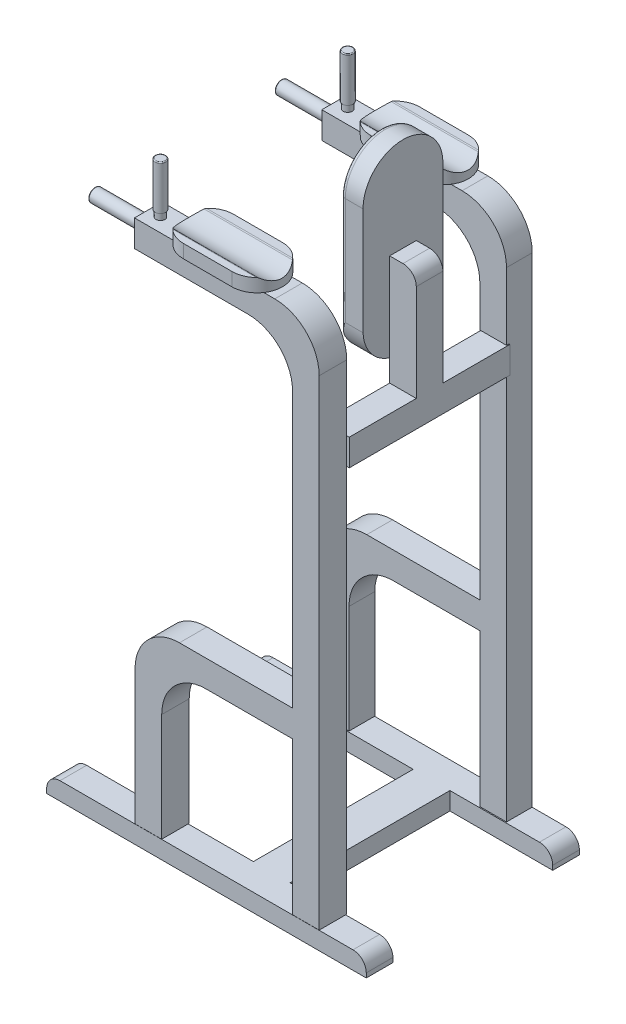
SolidWorks part; units mm, degrees
other "Camera1"
other "Camera2"
ref_plane "Front Plane" through (0, 0, 0) normal (0, 0, 1) x (1, 0, 0)
ref_plane "Top Plane" through (0, 0, 0) normal (0, 1, 0) x (1, 0, 0)
ref_plane "Right Plane" through (0, 0, 0) normal (1, 0, 0) x (0, 0, -1)
sketch "Sketch1" plane through (0, 0, 0) normal (0, 1, 0) x (1, 0, 0)
  line L0 (0, 0) -> (0, 76.2)
  line L1 (0, 76.2) -> (914.4, 76.2)
  line L2 (914.4, 76.2) -> (914.4, 0)
  line L3 (914.4, 0) -> (620.3894, 0)
  line L4 (620.3894, 0) -> (620.3894, -457.2)
  line L5 (620.3894, -457.2) -> (914.4, -457.2)
  line L6 (914.4, -457.2) -> (914.4, -533.4)
  line L7 (914.4, -533.4) -> (0, -533.4)
  line L8 (0, -533.4) -> (0, -457.2)
  line L9 (0, -457.2) -> (515.1929, -457.2)
  line L10 (515.1929, -457.2) -> (515.1929, 0)
  line L11 (515.1929, 0) -> (0, 0)
  dimension "D1" = 914.4
  dimension "D2" = 76.2
  dimension "D3" = 76.2
  dimension "D4" = 457.2
extrude "Boss-Extrude1" add sketch "Sketch1" along normal blind 50.8
fillet "Fillet1" radius 38.1 4 edges at (914.4, 50.8, 495.3) (914.4, 50.8, -38.1) (0, 50.8, -38.1) (0, 50.8, 495.3)
ref_plane "Plane1" through (0, 0, 535.94) normal (0, 0, 1) x (1, 0, 0)
sketch "Sketch2" plane through (0, 0, 535.94) normal (0, 0, 1) x (1, 0, 0)
  line L0 (331.6555, 53.7812) -> (331.6555, 362.6365)
  line L1 (458.6555, 489.6365) -> (706.0055, 489.6365)
  line L2 (706.0055, 489.6365) -> (706.0055, 53.7812)
  line L3 (706.0055, 53.7812) -> (782.2055, 53.7812)
  line L4 (782.2055, 53.7812) -> (782.2055, 1427.3864)
  line L5 (655.2055, 1554.3864) -> (253.8099, 1554.3864)
  line L6 (253.8099, 1554.3864) -> (253.8099, 1478.1864)
  line L7 (253.8099, 1478.1864) -> (579.0055, 1478.1864)
  line L8 (706.0055, 1351.1864) -> (706.0055, 565.8365)
  line L9 (706.0055, 565.8365) -> (382.4555, 565.8365)
  line L10 (255.4555, 438.8365) -> (255.4555, 53.7812)
  line L11 (255.4555, 53.7812) -> (331.6555, 53.7812)
  arc A0 (331.6555, 362.6365) -> (458.6555, 489.6365) centre (458.6555, 362.6365) cw
  arc A1 (382.4555, 565.8365) -> (255.4555, 438.8365) centre (382.4555, 438.8365) ccw
  arc A2 (782.2055, 1427.3864) -> (655.2055, 1554.3864) centre (655.2055, 1427.3864) ccw
  arc A3 (579.0055, 1478.1864) -> (706.0055, 1351.1864) centre (579.0055, 1351.1864) cw
  point P18 (782.2055, 1554.3864)
  dimension "D6" = 127
  dimension "D1" = 528.3956
  dimension "D2" = 76.2
  dimension "D3" = 76.2
  dimension "D4" = 76.2
  dimension "D5" = 76.2
extrude "Boss-Extrude2" add sketch "Sketch2" against normal blind 609.6 separate body
sketch "Sketch3" plane through (255.4555, 0, 0) normal (-1, 0, 0) x (0, 0, 1)
  line L0 (0, 50.8) -> (0, 1554.3864)
  line L1 (-73.66, 1554.3864) -> (535.94, 1554.3864) construction
  line L2 (0, 50.8) -> (457.2, 50.8)
  line L3 (457.2, 50.8) -> (457.2, 1554.3864)
  line L4 (457.2, 1554.3864) -> (0, 1554.3864)
extrude "Cut-Extrude1" cut sketch "Sketch3" against normal through all both and the other way through all
ref_plane "Plane2" through (784.7455, 0, 0) normal (1, 0, 0) x (0, 0, -1)
sketch "Sketch6" plane through (784.7455, 0, 0) normal (1, 0, 0) x (0, 0, -1)
  line L0 (7.3557, 1234.749) -> (-184.4143, 1234.749)
  line L1 (-452.3843, 1158.549) -> (7.3557, 1158.549)
  line L2 (7.3557, 1158.549) -> (7.3557, 1234.749)
  line L3 (-452.3843, 1234.749) -> (-452.3843, 1158.549)
  line L4 (-260.6143, 1234.749) -> (-260.6143, 1397.5306)
  line L5 (-260.6143, 1397.5306) -> (-184.4143, 1397.5306)
  line L6 (-184.4143, 1397.5306) -> (-184.4143, 1234.749)
  line L7 (-260.6143, 1234.749) -> (-452.3843, 1234.749)
  dimension "D1" = 76.2
  dimension "D2" = 76.2
  dimension "D3" = 191.77
  dimension "D4" = 191.77
  dimension "D5" = 76.2
extrude "Boss-Extrude3" add sketch "Sketch6" against normal blind 76.2
sketch "Sketch7" plane through (708.5455, 0, 0) normal (-1, 0, 0) x (0, 0, 1)
  line L0 (222.5143, 1397.5306) -> (222.5143, 1292.0473) construction
  line L1 (184.4143, 1397.5306) -> (260.6143, 1397.5306) construction
  line L2 (222.5143, 1292.0473) -> (222.5143, 1397.5306) construction
  line L3 (222.5143, 1397.5306) -> (222.5143, 1704.5869) construction
  line L4 (222.5143, 1704.5869) -> (222.5143, 1397.5306) construction
  line L5 (222.5143, 1397.5306) -> (108.2143, 1397.5306) construction
  line L6 (108.2143, 1397.5306) -> (222.5143, 1397.5306) construction
  line L7 (222.5143, 1397.5306) -> (336.8143, 1397.5306) construction
  line L8 (108.2143, 1397.5306) -> (108.2143, 1704.5869)
  line L9 (336.8143, 1397.5306) -> (336.8143, 1704.5869)
  arc A0 (108.2143, 1397.5306) -> (222.5143, 1292.0473) centre (218.1059, 1401.9389) ccw
  arc A1 (222.5143, 1292.0473) -> (336.8143, 1397.5306) centre (226.9227, 1401.9389) ccw
  arc A2 (108.2143, 1704.5869) -> (336.8143, 1704.5869) centre (222.5143, 1704.5869) cw
  dimension "D1" = 114.3
  dimension "D2" = 114.3
extrude "Boss-Extrude4" add sketch "Sketch7" along normal blind 63.5
sketch "Sketch8" plane through (0, 1397.5306, 0) normal (0, 1, 0) x (1, 0, 0)
  line L0 (708.5455, -184.4143) -> (708.5455, -260.6143)
  line L1 (708.5455, -260.6143) -> (784.7455, -260.6143)
  line L2 (784.7455, -260.6143) -> (784.7455, -184.4143)
  line L3 (784.7455, -184.4143) -> (708.5455, -184.4143)
extrude "Boss-Extrude5" add sketch "Sketch8" along normal blind 152.4
fillet "Fillet2" radius 38.1 1 edges at (784.7455, 1549.9306, 222.5143)
fillet "Fillet3" radius 12.7 3 edges at (645.0455, 1551.0587, 336.8143) (645.0455, 1551.0587, 108.2143) (645.0455, 1818.8869, 222.5143)
sketch "Sketch9" plane through (0, 1554.3864, 0) normal (0, 1, 0) x (1, 0, 0)
  line L1 (655.2055, -457.2) -> (253.8099, -457.2) construction
  line L2 (655.2055, 0) -> (253.8099, 0) construction
  circle A0 centre (288.5997, 39.37) radius 12.7
  circle A1 centre (288.5997, -496.57) radius 12.7
  dimension "D1" = 39.37
  dimension "D3" = 25.4
  dimension "1.55" = 39.37
extrude "Boss-Extrude6" add sketch "Sketch9" along normal blind 19.05
sketch "Sketch10" plane through (0, 1573.4364, 0) normal (0, 1, 0) x (1, 0, 0)
  circle A0 centre (288.5997, 39.37) radius 15.24
  circle A1 centre (288.5997, -496.57) radius 15.24
extrude "Boss-Extrude7" add sketch "Sketch10" along normal blind 127
fillet "Fillet5" radius 2.54 1 edges at (288.5997, 1700.4364, 511.81)
fillet "Fillet6" radius 2.54 1 edges at (288.5997, 1700.4364, -24.13)
sketch "Sketch11" plane through (0, 1554.3864, 0) normal (0, 1, 0) x (1, 0, 0)
  line L0 (424.8028, 73.66) -> (424.8028, -535.94) construction
  line L3 (655.2055, 73.66) -> (253.8099, 73.66) construction
  line L4 (-27.94, -535.94) -> (27.94, -535.94) construction
  line L7 (424.8028, 38.4588) -> (564.3599, 38.4588) construction
  line L10 (424.8028, 108.8486) -> (564.3599, 108.8486)
  line L11 (424.8028, -31.9309) -> (564.3599, -31.9309)
  line L12 (424.8028, -495.3784) -> (564.3599, -495.3784) construction
  line L13 (424.8028, -423.3604) -> (564.3599, -423.3604)
  line L14 (424.8028, -567.3964) -> (564.3599, -567.3964)
  arc A4 (424.8028, 108.8486) -> (424.8028, -31.9309) centre (424.8028, 38.4588) ccw
  arc A5 (564.3599, -31.9309) -> (564.3599, 108.8486) centre (564.3599, 38.4588) ccw
  arc A6 (424.8028, -423.3604) -> (424.8028, -567.3964) centre (424.8028, -495.3784) ccw
  arc A7 (564.3599, -567.3964) -> (564.3599, -423.3604) centre (564.3599, -495.3784) ccw
  point P8 (494.5813, 38.4588)
  point P10 (440.3064, 38.4588)
  point P14 (494.5813, -495.3784)
  point P15 (440.3064, -495.3784)
extrude "Boss-Extrude9" add sketch "Sketch11" along normal blind 38.1
sketch "Sketch12" plane through (784.7455, 0, 0) normal (1, 0, 0) x (0, 0, -1)
  circle A0 centre (-497.5169, 1656.3313) radius 79.8528
  circle A1 centre (36.2076, 1656.3313) radius 79.756
extrude "Cut-Extrude2" cut sketch "Sketch12" against normal blind 457.2
fillet "Fillet7" radius 6.35 2 edges at (494.5813, 1592.4864, -84.0076) (494.5813, 1592.4864, 11.5925)
fillet "Fillet8" radius 6.35 2 edges at (494.5813, 1592.4864, 545.4782) (494.5813, 1592.4864, 449.5555)
sketch "Sketch13" plane through (253.8099, 0, 0) normal (-1, 0, 0) x (0, 0, 1)
  line L0 (-73.66, 1554.3864) -> (0, 1478.1864) construction
  line L1 (457.2, 1554.3864) -> (535.94, 1478.1864) construction
  circle A0 centre (-36.83, 1516.2864) radius 19.05
  circle A1 centre (496.57, 1516.2864) radius 19.05
extrude "Boss-Extrude10" add sketch "Sketch13" along normal blind 152.4
fillet "Fillet9" radius 2.54 1 edges at (101.4099, 1516.2864, -17.78)
fillet "Fillet10" radius 2.54 1 edges at (101.4099, 1516.2864, 515.62)
